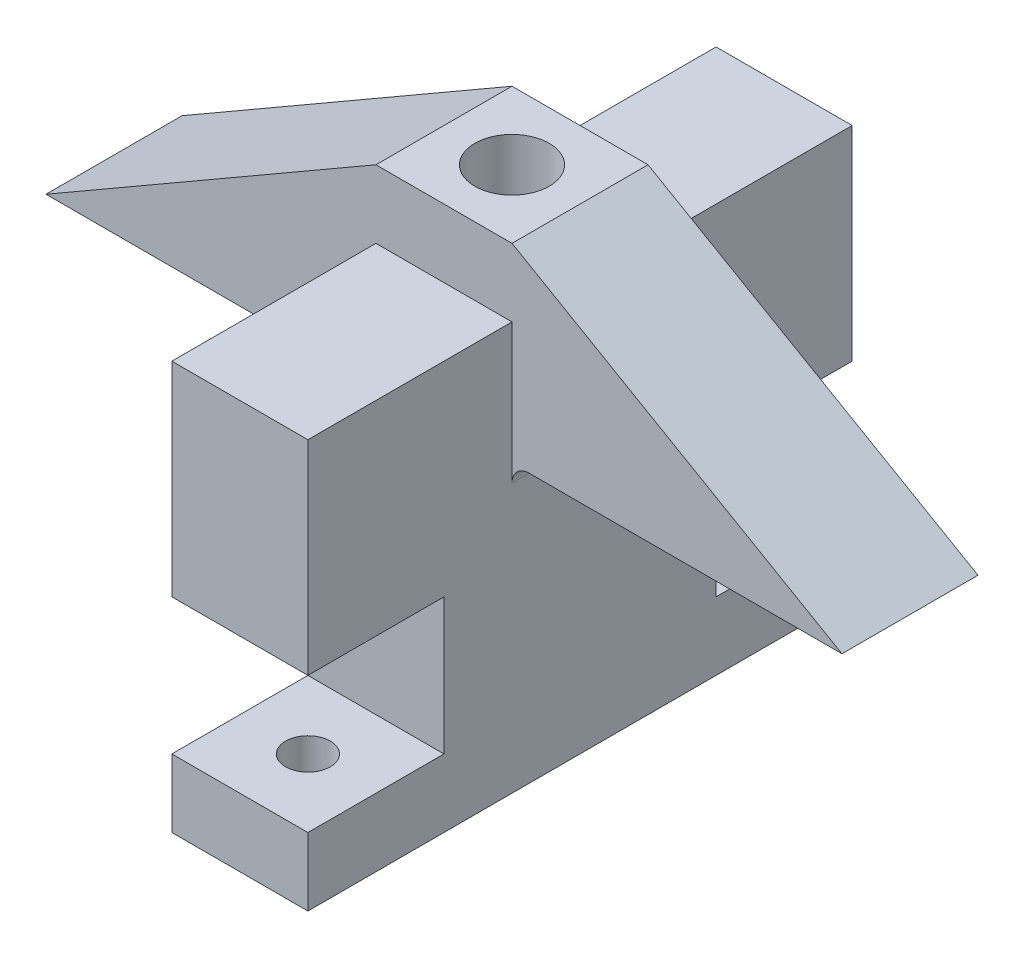
SolidWorks part; units mm, degrees
material "PET"
ref_plane "Front Plane" through (0, 0, 0) normal (0, 0, 1) x (1, 0, 0)
ref_plane "Top Plane" through (0, 0, 0) normal (0, 1, 0) x (1, 0, 0)
ref_plane "Right Plane" through (0, 0, 0) normal (1, 0, 0) x (0, 0, -1)
sketch "Sketch1" plane through (0, 0, 0) normal (0, 0, 1) x (1, 0, 0)
  line L0 (0, 0) -> (0, 53.34)
  line L1 (0, 53.34) -> (-61.5917, 53.34)
  line L2 (-61.5917, 53.34) -> (0, 88.9)
  line L3 (0, 88.9) -> (25.4, 88.9)
  line L4 (25.4, 88.9) -> (86.9917, 53.34)
  line L5 (86.9917, 53.34) -> (25.4, 53.34)
  line L6 (25.4, 53.34) -> (25.4, 0)
  line L7 (25.4, 0) -> (0, 0)
  point P9 (12.7, 88.9)
  point P10 (12.7, 0)
  dimension "D1" = 35.56
  dimension "D2" = 25.4
  dimension "D3" = 30
  dimension "D4" = 30
  dimension "D5" = 25.4
  dimension "D6" = 88.9
extrude "Boss-Extrude1" add sketch "Sketch1" along normal blind 25.4
sketch "Sketch2" plane through (0, 0, 25.4) normal (0, 0, 1) x (1, 0, 0)
  line L1 (0, 0) -> (25.4, 0)
  line L2 (0, 0) -> (0, 12.7)
  line L3 (0, 12.7) -> (25.4, 12.7)
  line L4 (25.4, 0) -> (25.4, 12.7)
  line L5 (25.4, 0) -> (25.4, 53.34) construction
  dimension "D1" = 12.7
extrude "Boss-Extrude2" add sketch "Sketch2" along normal blind 38.1
sketch "Sketch3" plane through (0, 0, 0) normal (0, 0, -1) x (-1, 0, 0)
  line L1 (-25.4, 0) -> (0, 0)
  line L2 (-25.4, 0) -> (-25.4, 12.7)
  line L3 (-25.4, 12.7) -> (0, 12.7)
  line L4 (0, 0) -> (0, 12.7)
  line L5 (0, 53.34) -> (0, 0) construction
  point P5 (0, 0)
  dimension "D1" = 12.7
extrude "Boss-Extrude3" add sketch "Sketch3" along normal blind 38.1
hole_wizard "Ø0.328in Dowel Hole1" positions "Sketch4" profile "Sketch5" hole size "Ø1.0" standard "ISO" end condition through all
sketch "Sketch4" plane through (0, 12.7, 0) normal (0, 1, 0) x (1, 0, 0)
  point P0 (12.7, 25.4)
  point P2 (12.7, -50.8)
  dimension "D1" = 12.7
  dimension "D2" = 12.7
  dimension "D3" = 12.7
  dimension "D4" = 12.7
sketch "Sketch5" plane through (12.7, 12.7, -25.4) normal (1, 0, 0) x (0, 0, 1)
  line L0 (0, 0) -> (0, 12.7)
  line L1 (0, 12.7) -> (4.1656, 12.7)
  line L2 (4.1656, 12.7) -> (4.1656, 0)
  line L5 (4.1656, 0) -> (0, 0)
  line L11 (0, -6.35) -> (0, 107.95) construction
  dimension "Thru Hole Dia." = 8.3312
  dimension "Thru Hole Depth" = 12.7
hole_wizard "Ø0.55in Dowel Hole2" positions "Sketch7" profile "Sketch6" hole size "Ø1.0" standard "ISO"
sketch "Sketch7" plane through (0, 88.9, 0) normal (0, 1, 0) x (1, 0, 0)
  point P0 (12.7, -12.7)
  dimension "D1" = 12.7
  dimension "D2" = 12.7
sketch "Sketch6" plane through (12.7, 88.9, 12.7) normal (1, 0, 0) x (0, 0, 1)
  line L0 (0, 0) -> (0, 39.2261)
  line L1 (0, 39.2261) -> (6.9469, 35.052)
  line L2 (6.9469, 35.052) -> (6.9469, 0)
  line L5 (6.9469, 0) -> (0, 0)
  line L10 (0, 39.2261) -> (-6.9469, 35.052) construction
  line L11 (0, -6.35) -> (0, 107.95) construction
  dimension "Hole Dia." = 13.8938
  dimension "Hole Depth" = 35.052
  dimension "Drill Angle" = 118
fillet "Fillet1" radius 3.175 2 edges at (25.4, 53.34, 12.7) (0, 53.34, 12.7)
sketch "Sketch8" plane through (0, 0, 25.4) normal (0, 0, 1) x (1, 0, 0)
  line L0 (25.4, 12.7) -> (25.4, 50.165) construction
  line L1 (0, 12.7) -> (25.4, 12.7)
  line L2 (0, 12.7) -> (0, 76.2)
  line L3 (0, 76.2) -> (25.4, 76.2)
  line L4 (25.4, 12.7) -> (25.4, 76.2)
  line L5 (0, 38.1) -> (25.4, 38.1)
  line M5 (0, 12.7) -> (25.4, 12.7)
  line M6 (25.4, 12.7) -> (25.4, 50.165)
  line M14 (0, 50.165) -> (0, 12.7)
  dimension "D1" = 63.5
  dimension "D2" = 25.4
extrude "Boss-Extrude4" add sketch "Sketch8" along normal blind 12.7 contours L5 L2 M5 M6 region at (12.7, 25.4, 25.4)
extrude "Boss-Extrude5" add sketch "Sketch8<3>" along normal blind 38.1 contours L5 L4 L3 L2 M14 region at (12.7, 57.15, 25.4)
sketch "Sketch8<3>" plane through (0, 0, 25.4) normal (0, 0, 1) x (1, 0, 0) same geometry as "Sketch8"
sketch "Sketch9" plane through (0, 0, 0) normal (0, 0, -1) x (-1, 0, 0)
  line L0 (-25.4, 38.1) -> (0, 38.1)
  line L1 (-25.4, 12.7) -> (0, 12.7)
  line L2 (-25.4, 12.7) -> (-25.4, 76.2)
  line L3 (-25.4, 76.2) -> (0, 76.2)
  line L4 (0, 12.7) -> (0, 76.2)
  line L5 (0, 38.1) -> (0, 12.7) construction
  point P7 (0, 0)
  line M6 (-25.4, 12.7) -> (0, 12.7)
  line M7 (0, 12.7) -> (0, 50.165)
  line M15 (-25.4, 50.165) -> (-25.4, 12.7)
  dimension "D1" = 25.4
  dimension "D2" = 63.5
extrude "Boss-Extrude6" add sketch "Sketch9" along normal blind 12.7 contours L0 M15 M6 M7 region at (12.7, 25.4, 0)
extrude "Boss-Extrude7" add sketch "Sketch9<3>" along normal blind 38.1 contours L4 L3 L2 L0 M7 M15 region at (12.7, 57.15, 0)
sketch "Sketch9<3>" plane through (0, 0, 0) normal (0, 0, -1) x (-1, 0, 0) same geometry as "Sketch9"
